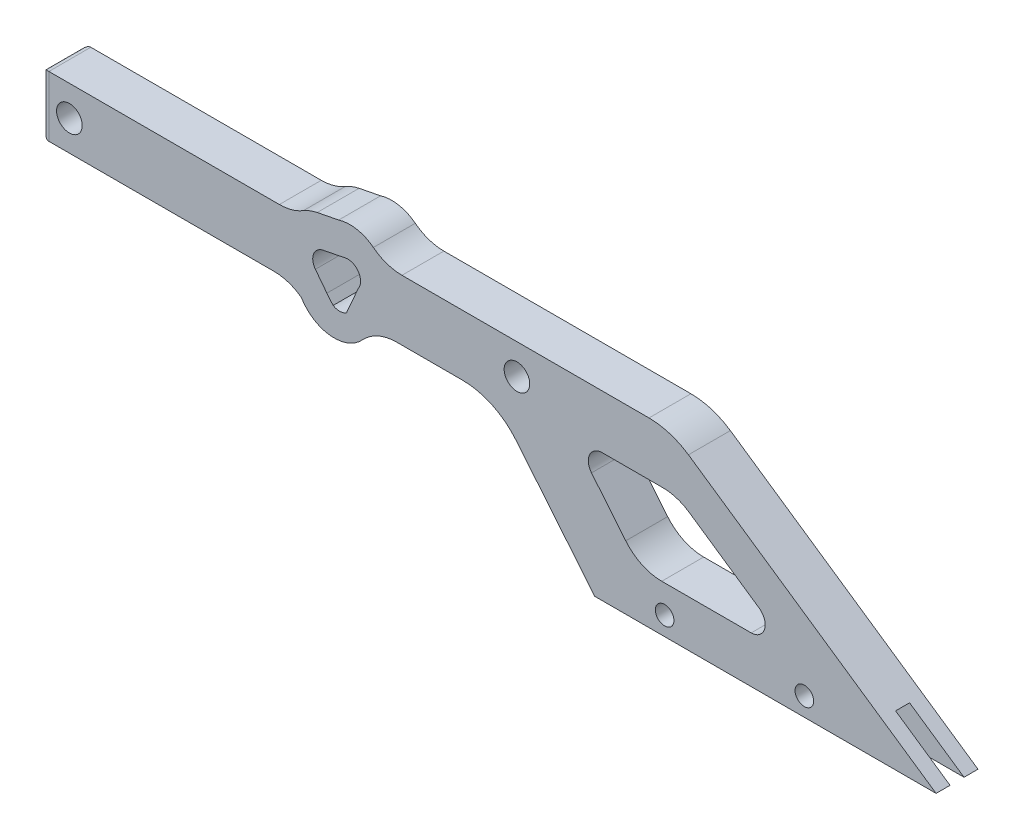
SolidWorks part; units mm, degrees
ref_plane "Front Plane" through (0, 0, 0) normal (0, 0, 1) x (1, 0, 0)
ref_plane "Top Plane" through (0, 0, 0) normal (0, 1, 0) x (1, 0, 0)
ref_plane "Right Plane" through (0, 0, 0) normal (1, 0, 0) x (0, 0, -1)
sketch "Sketch3" plane through (0, 0, 0) normal (0, 0, 1) x (1, 0, 0)
  line L6 (0, 0) -> (-70, 0) construction
  line L7 (-70, 4) -> (-70, 30) construction
  line L9 (-15.5885, 13) -> (-57, 13) construction
  line L15 (-57, 42.3999) -> (-57, 43) construction
  line L16 (-57, 43) -> (-192, 43)
  line L18 (-90, 30) -> (-90, 43) construction
  line L19 (-90, 36.5) -> (-90, -3.5) construction
  line L20 (-90, -3.5) -> (-131.1, -3.5) construction
  line L21 (-131.1, -3.5) -> (-131.1, 36.5) construction
  line L22 (-130.8074, 31.6129) -> (-133.2788, 34.8221)
  line L23 (-192, 43) -> (-192, 30)
  line L24 (-90, 36.5) -> (-176.1, 36.5) construction
  line L25 (0, 0) -> (0, 4) construction
  line L27 (-126.5827, 40.1978) -> (-131.6341, 39.1976)
  line L28 (0, 13) -> (-57, 13) construction
  line L30 (-118.5922, 34.7536) -> (-122.1392, 28.1801)
  line L31 (-136.2901, 28.0792) -> (-138.4287, 30.8562)
  line L32 (-128.2769, 46.4886) -> (-132.8967, 45.5738)
  line L35 (-57, 13) -> (-57, 42.3999) construction
  line L36 (-57, 13) -> (-57, 43) construction
  line L37 (-70, 30) -> (-90, 30) construction
  line L38 (-70, 30) -> (-192, 30) construction
  line L39 (-57, 43) -> (0, 4)
  line L41 (-109.2425, 30) -> (-113.8462, 30) construction
  line L42 (-113.8462, 30) -> (-192, 30)
  line L43 (-113.8462, 30) -> (-94.6383, 30)
  line L44 (-94.6383, 30) -> (-73.2851, 4)
  line L45 (-73.2851, 4) -> (0, 4)
  line L46 (-73.2851, 4) -> (-70, 0) construction
  line L47 (-70, 0) -> (-70, 4) construction
  line L48 (-70, 0) -> (-70, 30) construction
  line L49 (-131.1, 36.5) -> (-128.0493, 32.5386) construction
  line L50 (-131.1, 36.5) -> (-126.1952, 37.4712) construction
  line L51 (-124.3333, 37.8016) -> (-127.8053, 31.3673) construction
  line L52 (-130.8074, 31.6129) -> (-129.4705, 30)
  line L53 (-126.6281, 30) -> (-124.0601, 35.8756)
  circle A0 centre (-90, 36.5) radius 2.75
  arc A1 (-131.6341, 39.1976) -> (-133.2788, 34.8221) centre (-131.1, 36.5) ccw
  circle A5 centre (-176.1, 36.5) radius 2.75 construction
  circle A6 centre (-186.1, 36.5) radius 2.75
  arc A8 (-118.7111, 34.5331) -> (-109.2425, 30) centre (-131.1, -3.5) ccw construction
  arc A11 (-136.2901, 28.0792) -> (-122.1392, 28.1801) centre (-129.2441, 32.2515) ccw
  arc A12 (-132.8967, 45.5738) -> (-138.4287, 30.8562) centre (-131.1, 36.5) ccw
  arc A13 (-128.2769, 46.4886) -> (-118.5922, 34.7536) centre (-125.8867, 38.5973) cw
  arc A14 (-109.2425, 30) -> (-118.7111, 34.5331) centre (-131.1, -3.5) ccw construction
  circle A15 centre (-196.1, 36.5) radius 2.75 [skipped]
  arc A16 (-126.5827, 40.1978) -> (-124.3333, 37.8016) centre (-125.8867, 38.5973) cw construction
  arc A17 (-130.8074, 31.6129) -> (-127.8053, 31.3673) centre (-129.2441, 32.2515) ccw construction
  arc A18 (-129.4705, 30) -> (-126.6281, 30) centre (-128.0493, 32.5386) ccw
  arc A19 (-124.0601, 35.8756) -> (-127.1644, 40.0827) centre (-126.3394, 37.4426) ccw
  arc A20 (-128.9397, 36.5) -> (-128.9174, 36.4404) centre (-126.3394, 37.4426) ccw
  dimension "D7" = 45
  dimension "D8" = 135
  dimension "D12" = 70
  dimension "D3" = 5.5
  dimension "D14" = 2.75
  dimension "D15" = 5
  dimension "D19" = 96.1
  dimension "D1" = 13
  dimension "D2" = 20
  dimension "D4" = 40
  dimension "D5" = 41.1
  dimension "D9" = 30
  dimension "D10" = 4
  dimension "D11" = 5
  dimension "D13" = 52.4
  dimension "D6" = 11.2
  dimension "D16" = 10
  dimension "D17" = 6.5
  dimension "D18" = 3
extrude "Boss-Extrude3" add sketch "Sketch3" along normal mid plane 9 contours L16 A13 L30 L7 L6 L25 L9 L15 A0 | A12 L16 L23 L31 A6 A5 | A13 L16 A12 L31 L30 L27 L22 A1 | L31 A11 L30 | A13 L32 A12 L16 region at (-61.9346, 23.3064, 0) region at (-117.9092, 38.9099, 0) region at (-127.7127, 44.519, 0) region at (-165.0207, 36.5002, 0) region at (-129.3042, 27.5254, 0)
fillet "Fillet13" radius 15 2 edges at (-57, 43, 0) (-94.6383, 30, 0)
fillet "Fillet14" radius 10 4 edges at (-118.9153, 43, 0) (-137.6812, 43, 0) (-137.7693, 30, 0) (-121.1572, 30, 0)
fillet "Fillet15" [suppressed] radius 3
sketch "Sketch6" plane through (0, 4, 0) normal (0, -1, 0) x (1, 0, 0)
  line L0 (0, 4.5) -> (0, -4.5) construction
  line L1 (0, 1.5) -> (-69.2851, 1.5)
  line L2 (0, 1.5) -> (0, -1.5)
  line L3 (0, -1.5) -> (-69.2851, -1.5)
  line L4 (-69.2851, 1.5) -> (-69.2851, -1.5)
  line L5 (0, 1.5) -> (-69.2851, -1.5) construction
  line L6 (0, -1.5) -> (-69.2851, 1.5) construction
  point P4 (-34.6426, 0)
  point P7 (0, 0)
  dimension "D1" = 3
  dimension "D2" = 69.2851
extrude "Cut-Extrude3" cut sketch "Sketch6" against normal blind 8 contours L1 L4 L3 L2
sketch "Sketch7" plane through (0, 0, 4.5) normal (0, 0, 1) x (1, 0, 0)
  line L0 (-58.2851, 8) -> (-28.2851, 8) construction
  line L1 (-73.2851, 4) -> (0, 4) construction
  dimension "D1" = 4
  dimension "D2" = 30
  dimension "D3" = 15
hole_wizard "Ø3.0mm Dowel Hole1" positions "Sketch8" profile "Sketch9" hole size "Ø3.0" standard "ANSI Metric"
sketch "Sketch8" plane through (0, 0, 4.5) normal (0, 0, 1) x (1, 0, 0)
  point P0 (-28.2851, 8)
  point P3 (-58.2851, 8)
sketch "Sketch9" plane through (-28.2851, 8, 4.5) normal (1, 0, 0) x (0, -1, 0)
  line L0 (0, 0) -> (0, 10.2017)
  line L1 (0, 10.2017) -> (2, 9)
  line L2 (2, 9) -> (2, 0)
  line L5 (2, 0) -> (0, 0)
  line L10 (0, 10.2017) -> (-2, 9) construction
  line L11 (0, -6.35) -> (0, 107.95) construction
  dimension "Hole Dia." = 4
  dimension "Hole Depth" = 9
  dimension "Drill Angle" = 118
sketch "Sketch10" plane through (0, 0, 4.5) normal (0, 0, 1) x (1, 0, 0)
  line L5 (-78.0189, 31.5158) -> (-55.6, 31.5158)
  line L6 (-55.6, 31.5158) -> (-30, 14)
  line L7 (-30, 14) -> (-63.6336, 14)
  line L8 (-63.6336, 14) -> (-78.0189, 31.5158)
  line L9 (-90.1377, 24.52) -> (-73.2851, 4) construction
  line L10 (-53.1702, 40.3796) -> (0, 4) construction
  line L11 (-61.6405, 43) -> (-114.6861, 43) construction
  line L12 (-73.2851, 4) -> (0, 4) construction
  dimension "D1" = 33.6336
  dimension "D2" = 10
  dimension "D3" = 30
extrude "Cut-Extrude4" cut sketch "Sketch10" against normal up to surface (9 mm away) up to face at (-26.2851, 8, -4.5)
fillet "Fillet16" radius 3 2 edges at (-78.0189, 31.5158, 0) (-30, 14, 0)
fillet "Fillet17" radius 10 2 edges at (-63.6336, 14, 0) (-55.6, 31.5158, 0)
fillet "Fillet18" radius 1.5 4 edges at (-192, 43, 0) (-192, 36.5, 4.5) (-192, 30, 0) (-192, 36.5, -4.5)
